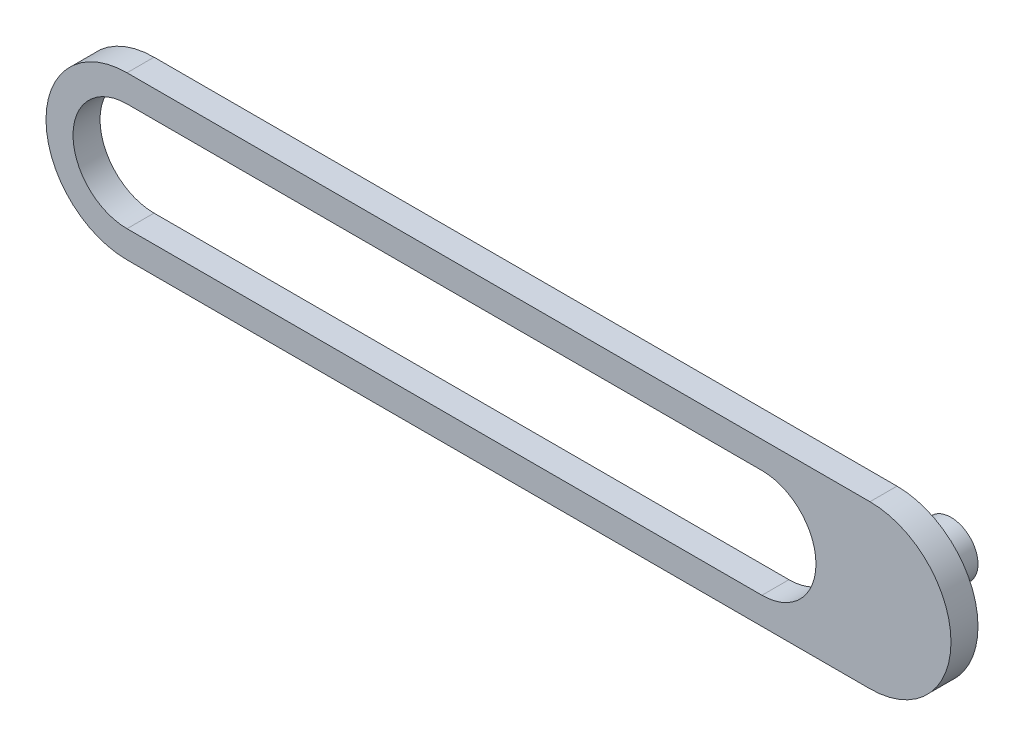
SolidWorks part; units mm, degrees
ref_plane "Front Plane" through (0, 0, 0) normal (0, 0, 1) x (1, 0, 0)
ref_plane "Top Plane" through (0, 0, 0) normal (0, 1, 0) x (1, 0, 0)
ref_plane "Right Plane" through (0, 0, 0) normal (1, 0, 0) x (0, 0, -1)
sketch "Sketch1" plane through (0, 0, 0) normal (0, 0, 1) x (1, 0, 0)
  line L0 (70.6452, 0) -> (50.6452, 0) construction
  line L1 (70.6452, -15) -> (-66.9032, -15)
  line L2 (70.6452, 15) -> (-66.9032, 15)
  line L5 (-66.9032, -10) -> (50.6452, -10)
  line L9 (-66.9032, 10) -> (50.6452, 10)
  arc A0 (70.6452, -15) -> (70.6452, 15) centre (70.6452, 0) ccw
  arc A1 (-66.9032, 15) -> (-78.0836, 10) centre (-66.9032, 0) ccw
  arc A3 (50.6452, -10) -> (50.6452, 10) centre (50.6452, 0) ccw
  arc A4 (-78.0836, -10) -> (-66.9032, -15) centre (-66.9032, 0) ccw
  circle A6 centre (70.6452, 0) radius 5
  arc A7 (-66.9032, 10) -> (-66.9032, -10) centre (-66.9032, 0) ccw
  arc A8 (-66.9032, 15) -> (-66.9032, -15) centre (-66.9032, 0) ccw
  point P2 (0, 0)
  point P10 (-12.9677, 0)
  dimension "D1" = 20
  dimension "D2" = 15
extrude "Boss-Extrude1" add sketch "Sketch1" along normal blind 5 contours A1 A8 A4 L1 A0 L2 A6 A3 L5 A7 L9 | A6
extrude "Boss-Extrude2" add sketch "Sketch1<3>" against normal blind 10 contours A6
sketch "Sketch1<3>" plane through (0, 0, 0) normal (0, 0, 1) x (1, 0, 0) same geometry as "Sketch1"
sketch "Sketch2" plane through (0, 0, 5) normal (0, 0, 1) x (1, 0, 0)
  line L0 (-68.0177, 0) -> (50.6452, 0)
